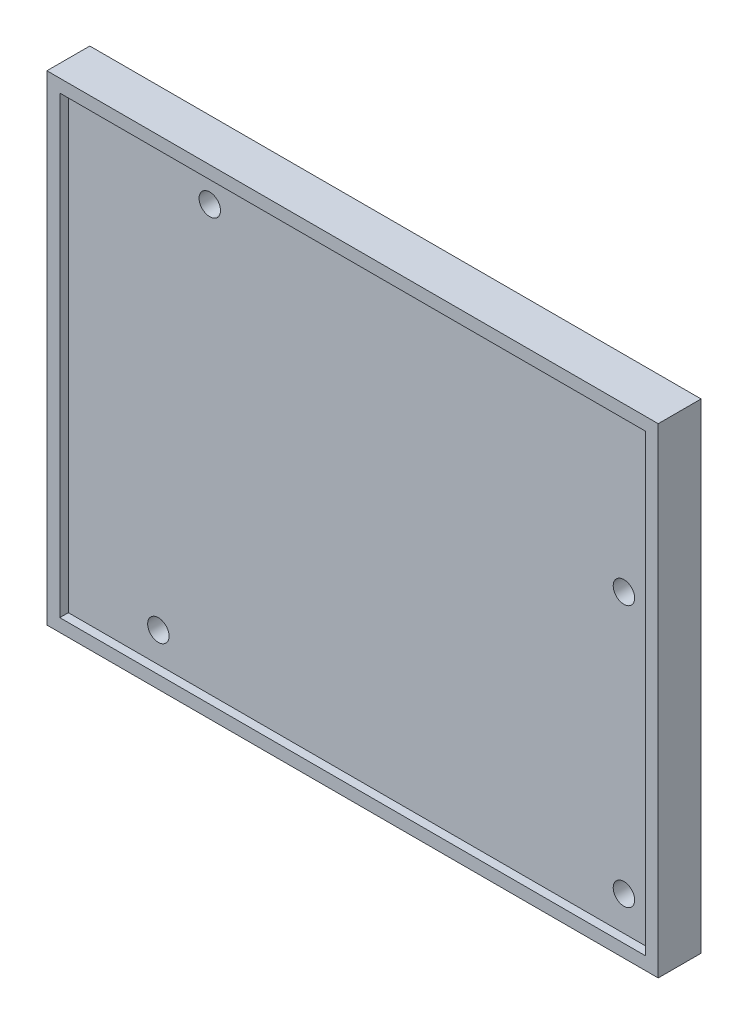
SolidWorks part; units mm, degrees
ref_plane "Front Plane" through (0, 0, 0) normal (0, 0, 1) x (1, 0, 0)
ref_plane "Top Plane" through (0, 0, 0) normal (0, 1, 0) x (1, 0, 0)
ref_plane "Right Plane" through (0, 0, 0) normal (1, 0, 0) x (0, 0, -1)
sketch "Sketch1" plane through (0, 0, 0) normal (0, 0, 1) x (1, 0, 0)
  line L5 (35.655, 28) -> (-35.655, 28)
  line L6 (35.655, 28) -> (35.655, -28)
  line L7 (35.655, -28) -> (-35.655, -28)
  line L8 (-35.655, 28) -> (-35.655, -28)
  line L9 (35.655, 28) -> (-35.655, -28) construction
  line L10 (35.655, -28) -> (-35.655, 28) construction
  point P0 (0, 0)
  dimension "D1" = 71.31
  dimension "D2" = 56
extrude "Boss-Extrude1" add sketch "Sketch1" along normal blind 5 contours L8 L7 L6 L5
sketch "Sketch2" plane through (0, 0, 5) normal (0, 0, 1) x (1, 0, 0)
  line L0 (-35.655, 28) -> (-35.655, -28) construction
  line L1 (35.655, -28) -> (-35.655, -28) construction
  line L2 (35.655, 28) -> (35.655, -28) construction
  line L3 (35.655, 28) -> (-35.655, 28) construction
  circle A0 centre (-23.655, -23) radius 1.25
  circle A1 centre (30.655, 8) radius 1.25
  circle A2 centre (-17.655, 23) radius 1.25
  circle A3 centre (30.655, -22.5) radius 1.25
  dimension "D3" = 2.5
  dimension "D4" = 2.5
  dimension "D5" = 2.5
  dimension "D6" = 2.5
  dimension "D1" = 12
  dimension "D2" = 5
  dimension "D7" = 5.5
  dimension "D8" = 5
  dimension "D9" = 20
  dimension "D10" = 5
  dimension "D11" = 18
  dimension "D12" = 5
extrude "Cut-Extrude1" cut sketch "Sketch2" against normal blind 5
sketch "Sketch3" plane through (0, 0, 5) normal (0, 0, 1) x (1, 0, 0)
  line L1 (34.155, -26.5) -> (-34.155, -26.5)
  line L2 (34.155, -26.5) -> (34.155, 26.5)
  line L3 (34.155, 26.5) -> (-34.155, 26.5)
  line L4 (-34.155, -26.5) -> (-34.155, 26.5)
  line L5 (34.155, -26.5) -> (-34.155, 26.5) construction
  line L6 (34.155, 26.5) -> (-34.155, -26.5) construction
  point P0 (0, 0)
  dimension "D1" = 53
  dimension "D2" = 68.31
extrude "Cut-Extrude2" cut sketch "Sketch3" against normal blind 1
